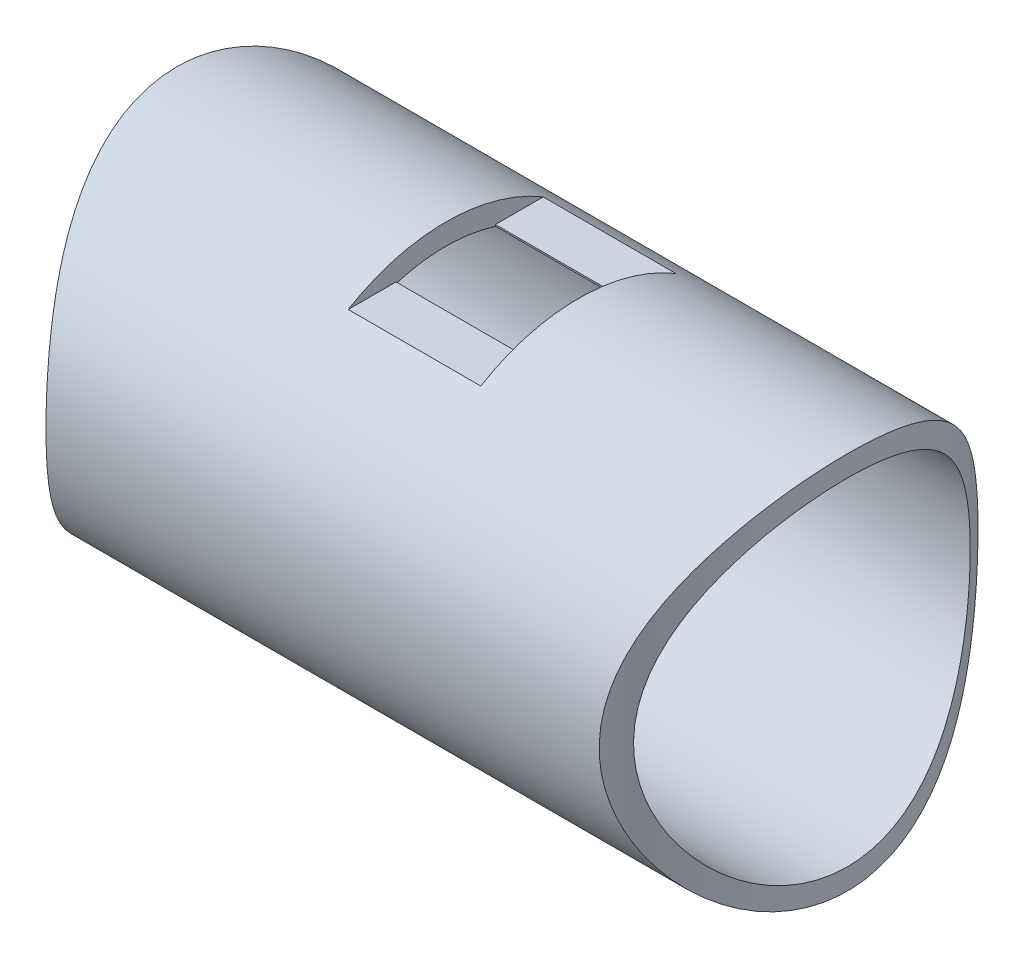
SolidWorks part; units mm, degrees
ref_plane "Front Plane" through (0, 0, 0) normal (0, 0, 1) x (1, 0, 0)
ref_plane "Top Plane" through (0, 0, 0) normal (0, 1, 0) x (1, 0, 0)
ref_plane "Right Plane" through (0, 0, 0) normal (1, 0, 0) x (0, 0, -1)
sketch "Sketch1" plane through (0, 0, 0) normal (1, 0, 0) x (0, 0, -1)
  circle A0 centre (0, 0) radius 57.15
  circle A1 centre (0, 0) radius 50.8
  dimension "D1" = 114.3
  dimension "D2" = 6.35
extrude "Boss-Extrude1" add sketch "Sketch1" along normal blind 101.15 and the other way blind 101.15
sketch "Sketch3" plane through (0, 0, 0) normal (0, 0, 1) x (1, 0, 0)
  line L0 (62.865, 0) -> (-62.865, 0) construction
  line L1 (-20, 59) -> (20, 59)
  line L2 (-20, 59) -> (-20, 49)
  line L3 (-20, 49) -> (20, 49)
  line L4 (20, 59) -> (20, 49)
  line L5 (0, -62.865) -> (0, 62.865) construction
  dimension "D1" = 49
  dimension "D2" = 10
  dimension "D3" = 40
  dimension "D4" = 20
extrude "Cut-Extrude3" cut sketch "Sketch3" against normal through all and the other way through all
sketch "Sketch5" plane through (0, 49, 0) normal (0, 1, 0) x (1, 0, 0)
  line L0 (-20, -29.413) -> (-20, 29.413) construction
  line L1 (20, -15) -> (-20, -15)
  line L2 (20, -15) -> (20, 15)
  line L3 (20, 15) -> (-20, 15)
  line L4 (-20, -15) -> (-20, 15)
  line L5 (20, -15) -> (-20, 15) construction
  line L6 (20, 15) -> (-20, -15) construction
  point P0 (0, 0)
  dimension "D1" = 30
extrude "Cut-Extrude5" cut sketch "Sketch5" against normal blind 18.15
sketch "Sketch6" plane through (0, 0, 0) normal (0, 1, 0) x (1, 0, 0)
  line L1 (126.0829, 122.4438) -> (-126.0829, 122.4438)
  line L2 (126.0829, 122.4438) -> (126.0829, -122.4438)
  line L3 (126.0829, -122.4438) -> (-126.0829, -122.4438)
  line L4 (-126.0829, 122.4438) -> (-126.0829, -122.4438)
  line L5 (126.0829, 122.4438) -> (-126.0829, -122.4438) construction
  line L6 (126.0829, -122.4438) -> (-126.0829, 122.4438) construction
  circle A0 centre (0, 0) radius 101.15
  dimension "D1" = 202.3
extrude "Cut-Extrude6" cut sketch "Sketch6" against normal through all and the other way through all
